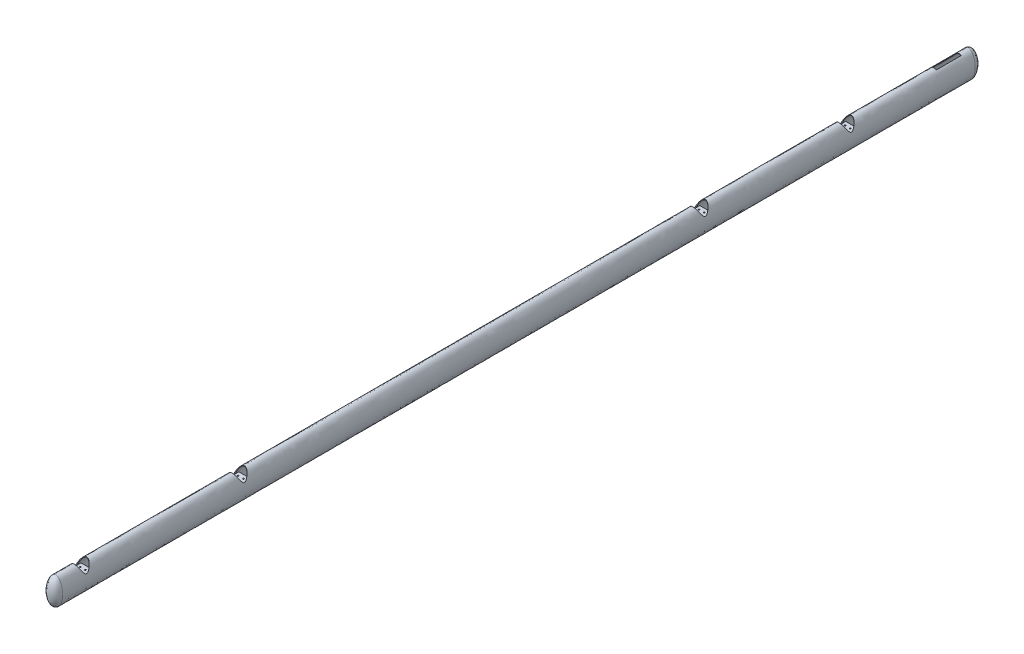
SolidWorks part; units mm, degrees
material "6061 Сплав"
ref_plane "Спереди" through (0, 0, 0) normal (0, 0, 1) x (1, 0, 0)
ref_plane "Сверху" through (0, 0, 0) normal (0, 1, 0) x (1, 0, 0)
ref_plane "Справа" through (0, 0, 0) normal (1, 0, 0) x (0, 0, -1)
sketch "Эскиз1" plane through (0, 0, 0) normal (0, 0, 1) x (1, 0, 0)
  line L0 (0, 286.5014) -> (0, -276.3874) construction
  ellipse E0 centre (234.2877, 0) end of major axis (234.2877, -30) minor radius 15
  ellipse E3 centre (234.2877, 0) end of major axis (234.2877, 28.8) minor radius 13.8
  dimension "D5" = 234.2877
extrude "Бобышка-Вытянуть1" add sketch "Эскиз1" along normal blind 2000
ref_plane "Плоскость1" through (0, 30, 0) normal (0, 1, 0) x (1, 0, 0)
sketch "Эскиз3" plane through (0, 30, 0) normal (0, 1, 0) x (1, 0, 0)
  circle A0 centre (-234.2877, -1946) radius 13.85
  circle A4 centre (234.2877, -270) radius 13.85
  circle A5 centre (234.2877, -590) radius 13.85
  circle A6 centre (234.2877, -1600) radius 13.85
  circle A7 centre (234.2877, -1946) radius 13.85
extrude "Вырез-Вытянуть1" cut sketch "Эскиз3" against normal blind 18
ref_plane "Плоскость2" through (234.2877, 0, 0) normal (1, 0, 0) x (0, 0, -1)
sketch "Эскиз4" plane through (234.2877, 0, 0) normal (1, 0, 0) x (0, 0, -1)
  line L0 (103.9999, 0) -> (-2069.6798, 0) construction
  line L1 (-1613.85, 30) -> (-1932.15, 30) construction
  line L2 (-1959.85, 12) -> (-1931.85, 12)
  line L3 (-1959.85, 12) -> (-1959.85, 8)
  line L4 (-1959.85, 8) -> (-1931.85, 8)
  line L5 (-1931.85, 12) -> (-1931.85, 8)
  line L6 (-1959.85, 30) -> (-1959.85, -38.8491) construction
  line L7 (-1586.15, 30) -> (-1586.15, -17.8904) construction
  line L8 (-603.85, 30) -> (-603.85, -10.0051) construction
  line L10 (-256.15, 30) -> (-256.15, -10.0051) construction
  line L11 (-1614.15, 12) -> (-1586.15, 12)
  line L12 (-1614.15, 12) -> (-1614.15, 8)
  line L13 (-1614.15, 8) -> (-1586.15, 8)
  line L14 (-1586.15, 12) -> (-1586.15, 8)
  line L15 (-603.85, 12) -> (-575.85, 12)
  line L16 (-603.85, 12) -> (-603.85, 8)
  line L17 (-603.85, 8) -> (-575.85, 8)
  line L18 (-575.85, 12) -> (-575.85, 8)
  line L19 (-283.85, 30) -> (-576.15, 30) construction
  line L20 (-284.15, 12) -> (-256.15, 12)
  line L21 (-284.15, 12) -> (-284.15, 8)
  line L22 (-284.15, 8) -> (-256.15, 8)
  line L23 (-256.15, 12) -> (-256.15, 8)
  dimension "D1" = 18
  dimension "D2" = 4
  dimension "D3" = 28
  dimension "D4" = 4
  dimension "D5" = 28
  dimension "D6" = 8
  dimension "D7" = 4
  dimension "D8" = 28
  dimension "D9" = 18
  dimension "D10" = 4
  dimension "D11" = 28
  dimension "D12" = 18
extrude "Бобышка-Вытянуть2" add sketch "Эскиз4" along normal up to next and the other way up to next
sketch3d "Трехмерный эскиз1"
  line L0 (0, 0, 0) -> (0, 0, 781.8375) construction
sketch "Эскиз6" plane through (0, 12, 0) normal (0, 1, 0) x (1, 0, 0)
  line L0 (207.6556, -1946) -> (272.459, -1946) construction
  line L1 (234.2877, -1946) -> (234.2877, -1918.1086) construction
  line L2 (228.6309, -1940.3431) -> (228.6309, -1951.6569) construction
  line L7 (239.9446, -1951.6569) -> (228.6309, -1940.3431) construction
  line L8 (239.9446, -1940.3431) -> (228.6309, -1951.6569) construction
  line L9 (228.6309, -1951.6569) -> (239.9446, -1951.6569) construction
  line L10 (239.9446, -1951.6569) -> (239.9446, -1940.3431) construction
  line L11 (239.9446, -1940.3431) -> (228.6309, -1940.3431) construction
  line L12 (234.2877, -1918.1086) -> (234.2877, 319.955) construction
  line L13 (234.2877, -50) -> (234.2877, 50) construction
  line L15 (234.2877, -1600) -> (234.2877, -1572.1086) construction
  line L16 (228.6309, -1594.3431) -> (228.6309, -1605.6569) construction
  line L17 (239.9446, -1605.6569) -> (228.6309, -1594.3431) construction
  line L18 (239.9446, -1594.3431) -> (228.6309, -1605.6569) construction
  line L19 (228.6309, -1605.6569) -> (239.9446, -1605.6569) construction
  line L20 (239.9446, -1605.6569) -> (239.9446, -1594.3431) construction
  line L21 (239.9446, -1594.3431) -> (228.6309, -1594.3431) construction
  line L22 (234.2877, -590) -> (234.2877, -571.5378) construction
  line L23 (228.6309, -584.3431) -> (228.6309, -595.6569) construction
  line L24 (239.9446, -595.6569) -> (228.6309, -584.3431) construction
  line L25 (239.9446, -584.3431) -> (228.6309, -595.6569) construction
  line L26 (228.6309, -595.6569) -> (239.9446, -595.6569) construction
  line L27 (239.9446, -595.6569) -> (239.9446, -584.3431) construction
  line L28 (239.9446, -584.3431) -> (228.6309, -584.3431) construction
  line L29 (234.2877, -270) -> (234.2877, -258.9739) construction
  line L30 (228.6309, -264.3431) -> (228.6309, -275.6569) construction
  line L31 (239.9446, -275.6569) -> (228.6309, -264.3431) construction
  line L32 (239.9446, -264.3431) -> (228.6309, -275.6569) construction
  line L33 (228.6309, -275.6569) -> (239.9446, -275.6569) construction
  line L34 (239.9446, -275.6569) -> (239.9446, -264.3431) construction
  line L35 (239.9446, -264.3431) -> (228.6309, -264.3431) construction
  arc A0 (248.0355, -1944.32) -> (220.54, -1944.32) centre (234.2877, -1946) ccw construction
  circle A1 centre (228.6309, -1940.3431) radius 1.5
  circle A2 centre (239.9446, -1940.3431) radius 1.5
  circle A3 centre (228.6309, -1951.6569) radius 1.5
  circle A4 centre (239.9446, -1951.6569) radius 1.5
  circle A5 centre (228.6309, -1594.3431) radius 1.5
  circle A6 centre (239.9446, -1594.3431) radius 1.5
  circle A7 centre (228.6309, -1605.6569) radius 1.5
  circle A8 centre (239.9446, -1605.6569) radius 1.5
  circle A9 centre (228.6309, -584.3431) radius 1.5
  circle A10 centre (239.9446, -584.3431) radius 1.5
  circle A11 centre (228.6309, -595.6569) radius 1.5
  circle A12 centre (239.9446, -595.6569) radius 1.5
  circle A13 centre (228.6309, -264.3431) radius 1.5
  circle A14 centre (239.9446, -264.3431) radius 1.5
  circle A15 centre (228.6309, -275.6569) radius 1.5
  circle A16 centre (239.9446, -275.6569) radius 1.5
  point P16 (234.2877, -590)
  point P20 (234.2877, -270)
  point P31 (234.2877, -1600)
  dimension "D3" = 3
  dimension "D5" = 3
  dimension "D7" = 3
  dimension "D9" = 3
  dimension "D1" = 0
  dimension "D2" = 16
  dimension "D4" = 16
  dimension "D6" = 16
  dimension "D8" = 16
extrude "Вырез-Вытянуть2" cut sketch "Эскиз6" against normal through all
sketch "Эскиз7" plane through (0, 0, 2000) normal (0, 0, 1) x (1, 0, 0)
  line L1 (234.2877, -50) -> (234.2877, 50) construction
  line L2 (234.2877, 30) -> (234.2877, 28.8)
  line L3 (234.2877, -28.8) -> (234.2877, -30)
  ellipse E0 centre (234.2877, 0) end of major axis (234.2877, 28.8) minor radius 13.8 (234.2877, -28.8) -> (234.2877, 28.8) ccw
  ellipse E2 centre (234.2877, 0) end of major axis (234.2877, 28.8) minor radius 13.8 construction
  ellipse E3 centre (234.2877, 0) end of major axis (234.2877, 30) minor radius 15 (234.2877, -30) -> (234.2877, 30) ccw
  ellipse E4 centre (234.2877, 0) end of major axis (234.2877, 30) minor radius 15 construction
  point P0 (234.2877, 0)
sketch3d "Трехмерный эскиз2"
  line L0 (234.2877, 30, 2000) -> (234.2877, -43.8, 2000) construction
revolve "Повернуть1" add sketch "Эскиз7" angle 180 about L0
sketch "Эскиз8" plane through (0, 0, 0) normal (0, 0, -1) x (-1, 0, 0)
  line L0 (-234.2877, 30) -> (-234.2877, -43.8) construction
  line L1 (-234.2877, 30) -> (-234.2877, 28.8)
  line L2 (-234.2877, -28.8) -> (-234.2877, -30)
  ellipse E0 centre (-234.2877, 0) end of major axis (-234.2877, 28.8) minor radius 13.8 (-234.2877, -28.8) -> (-234.2877, 28.8) ccw
  ellipse E1 centre (-234.2877, 0) end of major axis (-234.2877, 28.8) minor radius 13.8 construction
  ellipse E2 centre (-234.2877, 0) end of major axis (-234.2877, 28.8) minor radius 13.8 (-234.2877, -28.8) -> (-234.2877, 28.8) ccw construction
  ellipse E3 centre (-234.2877, 0) end of major axis (-234.2877, 30) minor radius 15 (-234.2877, -30) -> (-234.2877, 30) ccw
  ellipse E4 centre (-234.2877, 0) end of major axis (-234.2877, 30) minor radius 15 construction
  point P0 (-234.2877, 0)
sketch3d "Трехмерный эскиз3"
  line L0 (234.2877, 30, 0) -> (234.2877, -39.9503, 0) construction
revolve "Повернуть2" add sketch "Эскиз8" angle 180 about L0
sketch "Эскиз9" plane through (0, 0, 0) normal (0, 0, 1) x (1, 0, 0)
  line L0 (234.2877, 30) -> (234.2877, -62.4347) construction
  line L1 (239.3843, 38.8275) -> (224.3843, 12.8467)
  dimension "D1" = 30
  dimension "D2" = 30
sketch "Эскиз10" plane through (0, 30, 0) normal (0, 1, 0) x (1, 0, 0)
  line L0 (234.2877, 15) -> (234.2877, -77.3825) construction
  line L2 (229.0377, -76) -> (239.5377, -76)
  line L3 (229.0377, -76) -> (229.0377, -21)
  line L4 (229.0377, -21) -> (239.5377, -21)
  line L5 (239.5377, -76) -> (239.5377, -21)
  line L6 (229.0377, -76) -> (239.5377, -21) construction
  line L7 (229.0377, -21) -> (239.5377, -76) construction
  arc A0 (249.2877, 0) -> (219.2877, 0) centre (234.2877, 0) ccw construction
  point P5 (234.2877, -48.5)
  dimension "D1" = 10.5
  dimension "D2" = 55
  dimension "D3" = 36
extrude "Вырез-Вытянуть3" cut sketch "Эскиз10" against normal up to next
